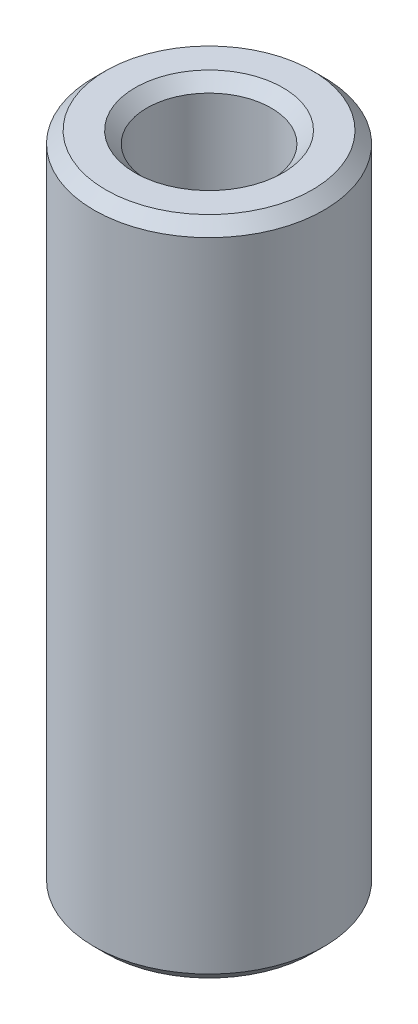
SolidWorks part; units mm, degrees
ref_plane "Front Plane" through (0, 0, 0) normal (0, 0, 1) x (1, 0, 0)
ref_plane "Top Plane" through (0, 0, 0) normal (0, 1, 0) x (1, 0, 0)
ref_plane "Right Plane" through (0, 0, 0) normal (1, 0, 0) x (0, 0, -1)
sketch "Sketch1" plane through (0, 0, 0) normal (0, 1, 0) x (1, 0, 0)
  circle A0 centre (0, 0) radius 5
  dimension "SLEEVE_OD" = 10
extrude "Boss-Extrude1" add sketch "Sketch1" along normal blind 28.7579
sketch "Sketch2" plane through (0, 0, 0) normal (0, 1, 0) x (1, 0, 0)
  circle A0 centre (0, 0) radius 2.7034
  dimension "BORE_D" = 5.4068
extrude "Cut-Extrude1" cut sketch "Sketch2" along normal through all
chamfer "Chamfer1" distance 0.5099 angle 45 4 edges at (0, 28.7579, 2.7034) (0, 0, 2.7034) (0, 0, 5) (0, 28.7579, 5)
